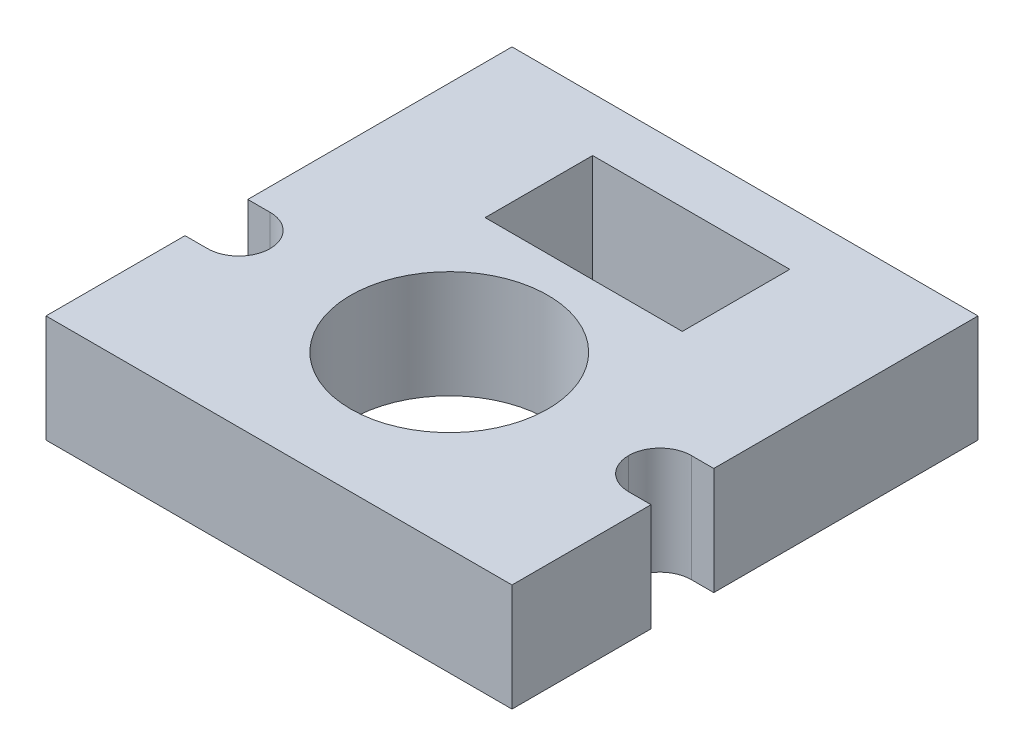
SolidWorks part; units mm, degrees
material "Acrílico (médio-alto impacto)"
ref_plane "Front" through (0, 0, 0) normal (0, 0, 1) x (1, 0, 0)
ref_plane "Top" through (0, 0, 0) normal (0, 1, 0) x (1, 0, 0)
ref_plane "Right" through (0, 0, 0) normal (1, 0, 0) x (0, 0, -1)
sketch "Esboço1" plane through (0, 0, 0) normal (0, 1, 0) x (1, 0, 0)
  line L0 (0, 13) -> (0, -3.5) construction
  line L1 (13, -13) -> (-13, -13)
  line L2 (13, -13) -> (13, 13)
  line L3 (13, 13) -> (-13, 13)
  line L4 (-13, -13) -> (-13, 13)
  line L5 (13, -13) -> (-13, 13) construction
  line L6 (13, 13) -> (-13, -13) construction
  line L7 (0, 13) -> (0, 10) construction
  line L8 (0, 10) -> (0, 4) construction
  line L9 (0, 10) -> (-5.5, 10)
  line L10 (0, 10) -> (5.5, 10)
  line L11 (-5.5, 10) -> (-5.5, 4)
  line L12 (-5.5, 4) -> (5.5, 4)
  line L13 (5.5, 4) -> (5.5, 10)
  line L14 (-13, -13) -> (-13, -3.5) construction
  line L15 (13, -13) -> (13, -3.4923) construction
  line L16 (13, -1.7423) -> (13, -5.2423)
  line L17 (13, -5.2423) -> (10, -5.2423)
  line L18 (10, -5.2423) -> (10, -1.7423)
  line L19 (10, -1.7423) -> (13, -1.7423)
  line L20 (13, -1.7423) -> (13, -5.2423)
  line L21 (-10, -1.7423) -> (-10, -5.2423)
  line L22 (-10, -5.2423) -> (-13, -5.2423)
  line L23 (-13, -5.2423) -> (-13, -1.7423)
  line L24 (-13, -1.7423) -> (-10, -1.7423)
  circle A0 centre (0, -3.5) radius 5.5
  point P0 (0, 0)
  point P20 (13, -3.4923)
  dimension "D4" = 3
  dimension "D1" = 26
  dimension "D2" = 26
  dimension "D3" = 16.5
  dimension "D5" = 6
  dimension "D6" = 5.5
  dimension "D7" = 5.5
  dimension "D8" = 3.5
  dimension "D9" = 2
extrude "Ressalto-extrusão1" add sketch "Esboço1" along normal blind 6 contours L21 L1 L3 A0 L13 L12 L11 L9 L10 region at (0, 0, 12.6323)
fillet "Filete1" radius 1.75 4 edges at (10, 3, 1.7423) (10, 3, 5.2423) (-10, 3, 1.7423) (-10, 3, 5.2423)
